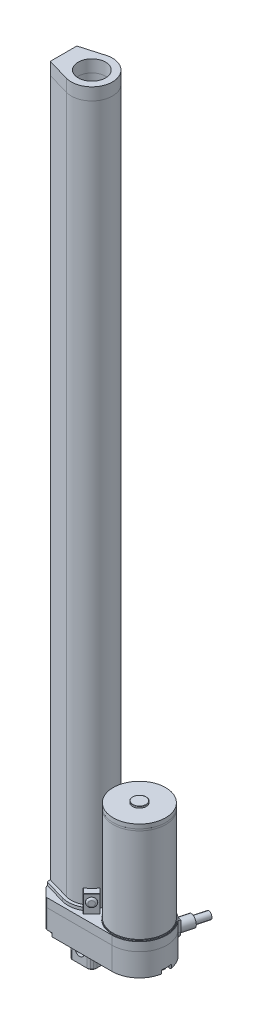
SolidWorks part; units mm, degrees
note: The reader was unsure of these and kept them because the rebuilt part matched: shared geometry of "Sketch1<3>", "Sketch41<11>", "Sketch41<12>", "Sketch45<3>".
ref_plane "Front Plane" through (0, 0, 0) normal (0, 0, 1) x (1, 0, 0)
ref_plane "Top Plane" through (0, 0, 0) normal (0, 1, 0) x (1, 0, 0)
ref_plane "Right Plane" through (0, 0, 0) normal (1, 0, 0) x (0, 0, -1)
sketch "Sketch1" plane through (0, 0, 0) normal (0, 1, 0) x (1, 0, 0)
  line L0 (0, 32.639) -> (7.239, 39.878)
  line L1 (7.239, 0) -> (55.118, 0)
  line L2 (0, 7.239) -> (0, 32.639)
  line L3 (7.239, 39.878) -> (55.118, 39.878)
  line L4 (7.239, 0) -> (0, 7.239)
  arc A0 (55.118, 0) -> (55.118, 39.878) centre (55.118, 19.939) ccw
  point P0 (0, 0)
  point P2 (0, 39.878)
  dimension "D1" = 55.118
  dimension "D2" = 39.878
extrude "Boss-Extrude1" add sketch "Sketch1" along normal blind 6.35
sketch "Sketch6" plane through (0, 6.35, 0) normal (0, 1, 0) x (1, 0, 0)
  circle A0 centre (55.118, 19.939) radius 19.431
extrude "Boss-Extrude4" add sketch "Sketch6" along normal blind 0.762 separate body contours A0
sketch "Sketch7" plane through (0, 7.112, 0) normal (0, 1, 0) x (1, 0, 0)
  circle A0 centre (55.118, 19.939) radius 19.05
  dimension "D1" = 38.1
extrude "Boss-Extrude5" add sketch "Sketch7" along normal blind 68.326 separate body
sketch "Sketch8" plane through (0, 75.438, 0) normal (0, 1, 0) x (1, 0, 0)
  circle A0 centre (55.118, 19.939) radius 4.953
  dimension "D1" = 9.906
fillet "Fillet6" radius 5.08 2 edges at (0, 3.175, -7.239) (0, 3.175, -32.639)
fillet "Fillet7" radius 1.905 2 edges at (7.239, 3.175, -39.878) (7.239, 3.175, 0)
sketch "Sketch15" plane through (0, 6.35, 0) normal (0, 1, 0) x (1, 0, 0)
  line L0 (35.5603, 29.0153) -> (35.5603, 29.0265)
  line L2 (0, 30.5348) -> (0, 9.3432) construction
  line L3 (0, 19.939) -> (0, 10.2869)
  line L4 (0, 19.939) -> (0, 29.591)
  line L5 (0, 10.2869) -> (16.412, 5.5423)
  line L7 (35.5603, 10.8628) -> (35.5603, 10.8515)
  line L10 (0, 29.591) -> (16.4119, 34.3357)
  arc A0 (16.412, 5.5423) -> (16.4119, 34.3357) centre (20.574, 19.939) ccw
ref_plane "Plane4" through (13.8375, 0, -51.6424) normal (0.2588, 0, -0.9659) x (0, -1, 0)
ref_plane "Plane5" through (12.5227, 0, -46.7355) normal (0.2588, 0, -0.9659) x (0, -1, 0)
sketch "Sketch23" plane through (12.5227, 0, -46.7355) normal (0.2588, 0, -0.9659) x (0, -1, 0)
  line L0 (-6.35, -67.5103) -> (-6.35, -28.6483) construction
  line L1 (-2.032, -53.8839) -> (5.588, -53.8839)
  line L2 (-2.032, -53.8839) -> (-2.032, -42.4539)
  line L3 (-2.032, -42.4539) -> (5.588, -42.4539)
  arc A0 (5.588, -53.8839) -> (5.588, -42.4539) centre (5.588, -48.1689) ccw
  dimension "D1" = 11.43
  dimension "D2" = 7.62
  dimension "D3" = 4.318
extrude "Boss-Extrude15" add sketch "Sketch23" along normal blind 6.35
sketch "Sketch24" plane through (14.1662, 0, -52.8692) normal (0.2588, 0, -0.9659) x (-0.9659, 0, -0.2588)
  circle A0 centre (-48.1689, -5.588) radius 4.064
  dimension "D1" = 8.128
extrude "Boss-Extrude16" add sketch "Sketch24" along normal blind 10.16
sketch "Sketch25" plane through (16.7959, 0, -62.683) normal (0.2588, 0, -0.9659) x (-0.9659, 0, -0.2588)
  circle A0 centre (-48.1689, -5.588) radius 2.54
  dimension "D1" = 5.08
extrude "Boss-Extrude17" add sketch "Sketch25" along normal blind 10.16
extrude "Boss-Extrude19" add sketch "Sketch1<3>" against normal blind 16.51 separate body
sketch "Sketch1<3>" plane through (0, 0, 0) normal (0, 1, 0) x (1, 0, 0) same geometry as "Sketch1"
fillet "Fillet13" radius 1.905 2 edges at (7.239, -8.255, 0) (7.239, -8.255, -39.878)
fillet "Fillet14" radius 5.08 2 edges at (0, -8.255, -32.639) (0, -8.255, -7.239)
sketch "Sketch26" plane through (0, -16.51, 0) normal (0, -1, 0) x (-1, 0, 0)
  line L4 (-20.574, 28.829) -> (-11.684, 28.829)
  line L5 (-20.574, 28.829) -> (-29.464, 28.829)
  line L6 (-11.684, 28.829) -> (-11.684, 11.049)
  line L7 (-11.684, 11.049) -> (-29.464, 11.049)
  line L8 (-29.464, 11.049) -> (-29.464, 28.829)
extrude "Boss-Extrude20" add sketch "Sketch26" along normal blind 18.796 separate body
chamfer "Chamfer1" distance 2.54 angle 45 4 edges at (29.464, -25.908, -28.829) (29.464, -25.908, -11.049) (11.684, -25.908, -11.049) (11.684, -25.908, -28.829)
fillet "Fillet15" radius 2.54 8 edges at (11.684, -25.908, -13.589) (14.224, -25.908, -11.049) (26.924, -25.908, -11.049) (29.464, -25.908, -13.589) (29.464, -25.908, -26.289) (26.924, -25.908, -28.829) (11.684, -25.908, -26.289) (14.224, -25.908, -28.829)
chamfer "Chamfer2" distance 0.762 angle 45 16 edges at (14.3041, -35.306, -11.2423) (20.574, -35.306, -11.049) (26.8439, -35.306, -11.2423) (28.194, -35.306, -12.319) (29.2707, -35.306, -13.6691) (29.464, -35.306, -19.939) (29.2707, -35.306, -26.2089) (28.194, -35.306, -27.559) (26.8439, -35.306, -28.6357) (20.574, -35.306, -28.829) (14.3041, -35.306, -28.6357) (12.954, -35.306, -27.559) (11.8773, -35.306, -26.2089) (11.684, -35.306, -19.939) (11.8773, -35.306, -13.6691) (12.954, -35.306, -12.319)
sketch "Sketch27" plane through (0, 0, -11.049) normal (0, 0, 1) x (1, 0, 0)
  circle A0 centre (20.574, -26.67) radius 3.175
extrude "Cut-Extrude3" cut sketch "Sketch27" against normal blind 19.05
sketch "Sketch28" plane through (0, 75.438, 0) normal (0, 1, 0) x (1, 0, 0)
  circle A0 centre (55.118, 19.939) radius 19.05
extrude "Boss-Extrude22" add sketch "Sketch28" along normal blind 1.27 separate body
sketch "Sketch29" plane through (0, 76.708, 0) normal (0, 1, 0) x (1, 0, 0)
  circle A0 centre (55.118, 19.939) radius 19.05
extrude "Boss-Extrude24" add sketch "Sketch29" along normal blind 3.048 separate body contours A0
extrude "Boss-Extrude25" add sketch "Sketch8" along normal blind 1.27 from surface at 4.318 contours A0 starting at face at (55.118, 79.756, -0.889)
fillet "Fillet16" radius 0.2286 1 edges at (55.118, 81.026, -14.986)
extrude "Boss-Extrude26" add sketch "Sketch15" along normal blind 508.381 separate body contours L5 A0 L10 L4 L3
sketch "Sketch32" plane through (0, 514.731, 0) normal (0, 1, 0) x (1, 0, 0)
  line L0 (0, 10.2869) -> (0, 29.591)
  line L1 (0, 29.591) -> (16.4119, 34.3357)
  line L2 (0, 10.2869) -> (16.412, 5.5423)
  arc A0 (16.412, 5.5423) -> (16.4119, 34.3357) centre (20.574, 19.939) ccw
  circle A1 centre (20.574, 19.939) radius 9.9695
  dimension "D1" = 19.939
extrude "Boss-Extrude27" add sketch "Sketch32" along normal blind 8.89 separate body
sketch "Sketch33" plane through (0, 523.621, 0) normal (0, 1, 0) x (1, 0, 0)
  circle A0 centre (20.574, 19.939) radius 10.033
  dimension "D1" = 20.066
sketch3d "3DSketch1" plane through (0, 0, 0) normal (0, 0, 1) x (1, 0, 0)
sketch "Sketch41" plane through (0, 6.35, 0) normal (0, 1, 0) x (1, 0, 0)
  line L0 (16.4119, 34.3357) -> (0, 29.591)
  line L1 (37.5429, 9.0662) -> (33.7712, 12.8379)
  line L2 (0.2737, 32.0497) -> (15.777, 36.5318)
  line L3 (37.5429, 9.0662) -> (31.2567, 2.78)
  line L4 (0, 29.591) -> (0, 30.5348)
  line L5 (0, 30.5348) -> (0.2737, 32.0497)
  line L6 (-0.6349, 31.7871) -> (15.777, 36.5318) construction
  line L7 (0, 19.9389) -> (7.9017, 19.9389)
  line L8 (31.2567, 2.78) -> (27.426, 6.6107)
  line L9 (0, 10.2869) -> (0, 29.591) construction
  line L10 (0, 10.2869) -> (0, 9.3431)
  line L12 (37.5429, 30.8116) -> (33.7712, 27.0399)
  line L13 (37.5429, 30.8116) -> (31.2567, 37.0978)
  line L14 (31.2567, 37.0978) -> (27.426, 33.2671)
  line L15 (0, 9.3431) -> (0.2737, 7.8281)
  line L16 (0.2737, 7.8281) -> (15.777, 3.3461)
  line L17 (16.4119, 5.5422) -> (0, 10.2869)
  line L18 (-0.6349, 8.0908) -> (15.7771, 3.3462) construction
  line L19 (27.426, 33.2671) -> (29.1122, 34.9533)
  line L20 (0, 29.591) -> (16.4119, 34.3357) construction
  line L21 (0, 10.2869) -> (16.412, 5.5423) construction
  arc A0 (16.4119, 34.3357) -> (33.7712, 27.0399) centre (20.574, 19.939) cw
  arc A1 (15.777, 36.5318) -> (29.1122, 34.9533) centre (20.574, 19.939) cw
  arc A2 (16.4119, 34.3357) -> (16.412, 5.5423) centre (20.574, 19.939) cw construction
  arc A3 (15.777, 36.5318) -> (15.7771, 3.3462) centre (20.574, 19.939) cw construction
  arc A4 (16.4119, 34.3357) -> (27.426, 33.2671) centre (20.574, 19.939) cw
  arc A5 (15.777, 3.3461) -> (29.1122, 4.9245) centre (20.574, 19.9389) ccw
  arc A6 (16.4119, 5.5422) -> (33.7712, 12.8379) centre (20.574, 19.9389) ccw
  line M5 (0, 30.5348) -> (0, 9.3432)
  arc M6 (0, 9.3432) -> (1.4879, 5.7511) centre (5.08, 9.3432) ccw
extrude "Boss-Extrude30" add sketch "Sketch41" along normal blind 2.159 separate body contours A1 L2 L5 L0 A0 L14 M5
extrude "Boss-Extrude31" add sketch "Sketch41<11>" along normal blind 2.159 separate body contours A6 L17 L15 L16 A5 L8 M5 M6
sketch "Sketch41<11>" plane through (0, 6.35, 0) normal (0, 1, 0) x (1, 0, 0) same geometry as "Sketch41"
extrude "Boss-Extrude33" add sketch "Sketch41<12>" along normal blind 12.7 separate body contours L14 A0 L12 L13 | A6 L8 L3 L1
sketch "Sketch41<12>" plane through (0, 6.35, 0) normal (0, 1, 0) x (1, 0, 0) same geometry as "Sketch41"
fillet "Fillet17" radius 0.2286 5 edges at (35.657, 19.05, -28.9258) (29.3413, 19.05, -35.1825) (34.3998, 19.05, -33.9547) (37.5429, 12.7, -30.8116) (31.2567, 12.7, -37.0978)
fillet "Fillet18" radius 0.2286 5 edges at (35.657, 19.05, -10.9521) (29.3413, 19.05, -4.6954) (37.5429, 12.7, -9.0662) (34.3998, 19.05, -5.9231) (31.2567, 12.7, -2.78)
sketch "Sketch43" plane through (34.1773, 0, -34.1773) normal (0.7071, 0, -0.7071) x (-0.7071, 0, -0.7071)
  circle A0 centre (-0.3147, 13.7414) radius 3.175
extrude "Boss-Extrude34" add sketch "Sketch43" along normal blind 1.27 separate body
fillet "Fillet19" radius 1.27 1 edges at (33.0527, 13.7414, -37.0978)
sketch "Sketch44" plane through (14.2383, 0, 14.2383) normal (0.7071, 0, 0.7071) x (0.7071, 0, -0.7071)
  circle A0 centre (28.5126, 13.7414) radius 3.175
extrude "Boss-Extrude35" add sketch "Sketch44" along normal blind 1.27 separate body
fillet "Fillet20" radius 1.27 1 edges at (37.5429, 13.7414, -7.2702)
sketch "Sketch45" plane through (0, -16.51, 0) normal (0, -1, 0) x (1, 0, 0)
  line L0 (4.0845, -36.7235) -> (6.681, -39.32)
  line L2 (6.681, -39.32) -> (1.4879, -34.1269) construction
  line L4 (55.118, -39.878) -> (8.0281, -39.878) construction
  line L5 (11.3938, -39.878) -> (8.0281, -39.878)
  line L6 (11.3938, 0) -> (8.0281, 0)
  line L7 (4.0845, -3.1545) -> (6.681, -0.558)
  arc A0 (11.2821, -38.9146) -> (11.3938, -39.878) centre (11.8197, -39.3405) ccw
  arc A1 (11.2821, -38.9146) -> (5.0443, -35.9783) centre (8.8543, -35.9783) ccw
  arc A2 (11.2821, -0.9634) -> (11.3938, 0) centre (11.8197, -0.5375) cw
  arc A3 (5.0443, -35.9783) -> (4.0845, -36.7235) centre (4.1918, -35.871) cw
  arc A4 (5.0443, -3.8997) -> (4.0845, -3.1545) centre (4.1918, -4.007) ccw
  arc A5 (11.2821, -0.9634) -> (5.0443, -3.8997) centre (8.8543, -3.8997) cw
  arc A6 (55.118, -39.878) -> (55.118, 0) centre (55.118, -19.939) ccw construction
  arc A7 (73.6621, -16.9922) -> (73.6621, -22.8858) centre (71.247, -19.939) ccw
  arc A8 (73.6621, -22.8858) -> (74.7121, -23.6317) centre (73.8141, -23.7837) cw
  arc A9 (73.6621, -16.9922) -> (74.7121, -16.2463) centre (73.8141, -16.0943) ccw
  arc A10 (8.0281, -39.878) -> (6.681, -39.32) centre (8.0281, -37.973) cw
  arc A11 (8.0281, 0) -> (6.681, -0.558) centre (8.0281, -1.905) ccw
  arc A12 (74.7121, -23.6317) -> (74.7121, -16.2463) centre (55.118, -19.939) ccw
  line M8 (1.4879, -34.1269) -> (6.681, -39.32)
  arc M9 (6.681, -39.32) -> (8.0281, -39.878) centre (8.0281, -37.973) ccw
  line M10 (8.0281, -39.878) -> (55.118, -39.878)
  line M12 (55.118, 0) -> (8.0281, 0)
  arc M13 (8.0281, 0) -> (6.681, -0.558) centre (8.0281, -1.905) ccw
  line M14 (6.681, -0.558) -> (1.4879, -5.7511)
extrude "Cut-Extrude5" cut sketch "Sketch45" against normal blind 2.54 contours A1 A3 A0 M8 M9 M10 | A5 A2 A4 M12 M13 M14
extrude "Cut-Extrude6" cut sketch "Sketch45<3>" against normal blind 2.54
sketch "Sketch45<3>" plane through (0, -16.51, 0) normal (0, -1, 0) x (1, 0, 0) same geometry as "Sketch45"
sketch "Sketch47" plane through (0, -13.97, 0) normal (0, -1, 0) x (-1, 0, 0)
  circle A0 centre (-8.8543, 35.9783) radius 2.54
  circle A1 centre (-8.8543, 3.8997) radius 2.54
  circle A2 centre (-71.247, 19.939) radius 2.54
extrude "Boss-Extrude36" add sketch "Sketch47" along normal blind 2.54 separate body
fillet "Fillet22" radius 1.524 1 edges at (8.8543, -16.51, -38.5183)
fillet "Fillet23" radius 1.524 1 edges at (8.8543, -16.51, -6.4397)
sketch "Sketch48" plane through (0, 0, 0) normal (-1, 0, 0) x (0, 0, 1)
  circle A0 centre (-19.939, 12.7) radius 3.81
extrude "Boss-Extrude37" add sketch "Sketch48" along normal blind 1.524
fillet "Fillet24" radius 1.524 1 edges at (-1.524, 12.7, -16.129)
fillet "Fillet25" radius 1.524 1 edges at (71.247, -16.51, -22.479)
sketch "Sketch49" plane through (0, 0, 0) normal (-1, 0, 0) x (0, 0, 1)
  line L0 (-19.9389, 514.731) -> (-19.9389, 509.778) construction
  line L1 (-29.591, 514.731) -> (-10.2869, 514.731) construction
  line L2 (-30.5348, 6.35) -> (-9.3432, 6.35) construction
  circle A0 centre (-19.9389, 509.778) radius 3.81
  dimension "Flat Head Screw" = 503.428
extrude "Cut-Extrude7" cut sketch "Sketch49" against normal blind 2.54
sketch "Sketch50" plane through (2.54, 0, 0) normal (-1, 0, 0) x (0, 0, 1)
  circle A0 centre (-19.9389, 509.778) radius 3.556
extrude "Boss-Extrude39" add sketch "Sketch50" along normal blind 2.54 contours A0
sketch "Sketch52" plane through (0, 0, -11.049) normal (0, 0, 1) x (1, 0, 0)
  circle A0 centre (20.574, 535.432) radius 3.175
  circle A1 centre (20.574, -26.67) radius 3.175 construction
  dimension "Hole to Hole" = 562.102
extrude "Cut-Extrude8" cut sketch "Sketch33" against normal blind 488.95
equation "\"Stroke\"= 18"
equation "\"D1@Boss-Extrude26\"= \"Stroke\" + 2.015"
equation "\"Flat Head Screw@Sketch49\"= \"Stroke\" + 1.82"
equation "\"Hole to Hole@Sketch52\"= \"Stroke\" + 4.13"
